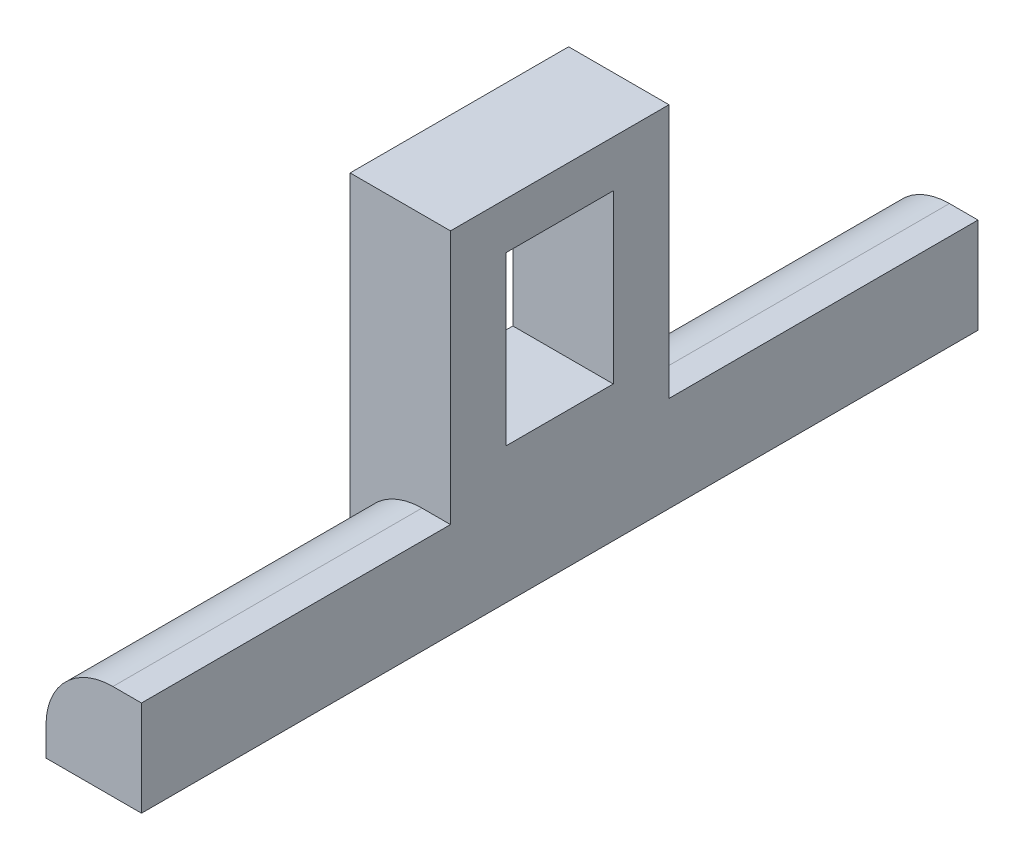
SolidWorks part; units mm, degrees
ref_plane "Front Plane" through (0, 0, 0) normal (0, 0, 1) x (1, 0, 0)
ref_plane "Top Plane" through (0, 0, 0) normal (0, 1, 0) x (1, 0, 0)
ref_plane "Right Plane" through (0, 0, 0) normal (1, 0, 0) x (0, 0, -1)
sketch "Sketch1" plane through (0, 0, 0) normal (1, 0, 0) x (0, 0, -1)
  line L0 (-3.2, 10) -> (-3.2, 0)
  line L1 (-3.2, 0) -> (-6.5301, 0)
  line L2 (-6.5301, 0) -> (-6.5301, 10)
  line L3 (-6.5301, 0) -> (-6.5301, -8.1222)
  line L4 (-6.5301, -8.1222) -> (6.5301, -8.1222)
  line L5 (0, 0) -> (0, 50000) construction
  line L6 (6.5301, -8.1222) -> (6.5301, 0)
  line L8 (6.5301, 0) -> (6.5301, 10)
  line L9 (3.2, 0) -> (6.5301, 0)
  line L10 (3.2, 10) -> (3.2, 0)
  line L11 (-3.2, 10) -> (3.2, 10)
  line L25 (6.5301, 10) -> (6.5301, 12.789)
  line L26 (-6.5301, 10) -> (-6.5301, 12.789)
  line L27 (-6.5301, 10) -> (-3.2, 10)
  line L28 (3.2, 10) -> (6.5301, 10)
  line L29 (3.2, 0) -> (-3.2, 0)
  line L30 (6.5301, 12.789) -> (-6.5301, 12.789)
  line L35 (-25, 12.1535) -> (-25, -1.9655) construction
  line L36 (25, 12.1535) -> (25, -1.9655) construction
  dimension "D3" = 8.1222
  dimension "D1" = 6.4
  dimension "D2" = 10
  dimension "D4" = 25
extrude "Boss-Extrude2" add sketch "Sketch1" against normal blind 6 contours L28 L10 L9 L8 | L27 L2 L1 L0 | L25 L30 L26 L27 L11 L28 | L9 L29 L1 L3 L4 L6 region at (0, 11.3945, 0) region at (0, 5, 4.8651) region at (0, -4.0611, 0) region at (0, 5, -4.8651)
sketch "Sketch2" plane through (0, 0, 6.5301) normal (0, 0, 1) x (1, 0, 0)
  line L1 (0, -8.1222) -> (-5.7072, -8.1222)
  line L2 (0, -8.1222) -> (0, -2.415)
  line L3 (0, -2.415) -> (-1.7072, -2.415)
  line L4 (-5.7072, -8.1222) -> (-5.7072, -6.415)
  arc A0 (-5.7072, -6.415) -> (-1.7072, -2.415) centre (-1.7072, -6.415) cw
  dimension "D1" = 4
  dimension "D2" = 5.7072
extrude "Boss-Extrude3" add sketch "Sketch2" along normal up to vertex (18.4699 mm away) and the other way up to vertex (31.5301 mm away) up to point (0, -1.9655, 25) other way up to point (0, -1.9655, -25)
